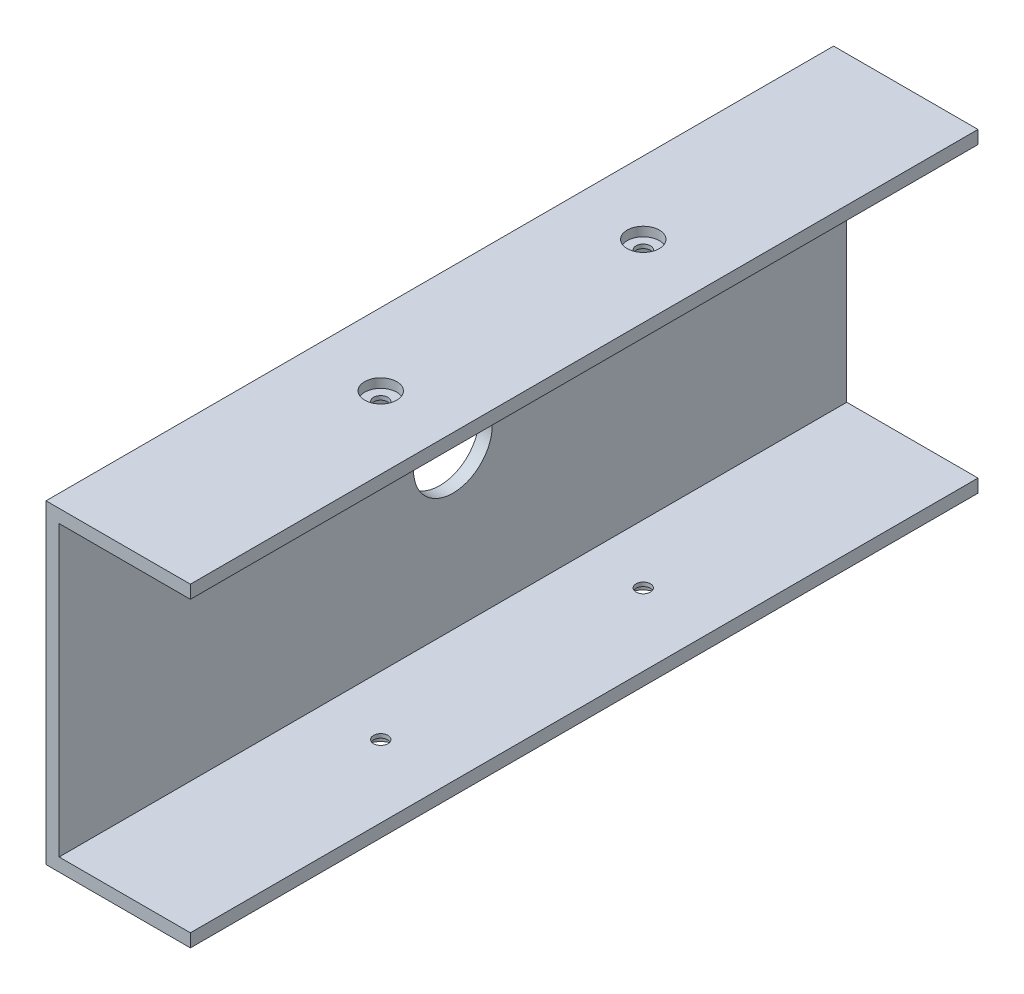
SolidWorks part; units mm, degrees
material "AISI 1035 Steel (SS)"
ref_plane "Front Plane" through (0, 0, 0) normal (0, 0, 1) x (1, 0, 0)
ref_plane "Top Plane" through (0, 0, 0) normal (0, 1, 0) x (1, 0, 0)
ref_plane "Right Plane" through (0, 0, 0) normal (1, 0, 0) x (0, 0, -1)
sketch "Sketch1" plane through (0, 0, 0) normal (0, 0, 1) x (1, 0, 0)
  line L0 (-64.6685, 67.8221) -> (-9.6685, 67.8221)
  line L1 (-9.6685, 67.8221) -> (-9.6685, 62.8221)
  line L2 (-9.6685, 62.8221) -> (-59.6685, 62.8221)
  line L3 (-59.6685, 62.8221) -> (-59.6685, -47.1779)
  line L4 (-59.6685, -47.1779) -> (-9.6685, -47.1779)
  line L5 (-9.6685, -47.1779) -> (-9.6685, -52.1779)
  line L6 (-9.6685, -52.1779) -> (-64.6685, -52.1779)
  line L7 (-64.6685, -52.1779) -> (-64.6685, 67.8221)
  point P6 (-64.6685, 7.8221)
  point P10 (-59.6685, 7.8221)
  dimension "D1" = 110
  dimension "D2" = 5
  dimension "D3" = 5
  dimension "D4" = 50
  dimension "D5" = 50
extrude "Boss-Extrude1" add sketch "Sketch1" along normal blind 300
sketch "Sketch2" plane through (0, 67.8221, 0) normal (0, 1, 0) x (1, 0, 0)
  line L0 (-64.6685, -300) -> (-64.6685, 0) construction
  line L1 (-9.6685, -300) -> (-9.6685, 0) construction
  line L2 (-9.6685, -300) -> (-64.6685, -300) construction
  point P0 (-37.1685, -200)
  point P1 (-32.1685, -200)
  dimension "D1" = 27.5
  dimension "D2" = 22.5
  dimension "D3" = 100
  dimension "D4" = 100
hole_wizard "CBORE for M5 Hex Head Bolt1" positions "Sketch3" profile "Sketch4" counterbore size "M5" standard "ISO"
sketch "Sketch3" plane through (0, 67.8221, 0) normal (0, 1, 0) x (1, 0, 0)
  point P0 (-37.1685, -200)
sketch "Sketch4" plane through (-37.1685, 67.8221, 200) normal (1, 0, 0) x (0, 0, 1)
  line L0 (0, 0) -> (0, 11.7024)
  line L1 (0, 11.7024) -> (2.75, 10.05)
  line L2 (2.75, 10.05) -> (2.75, 3.5)
  line L3 (2.75, 3.5) -> (6.119, 3.5)
  line L4 (6.119, 3.5) -> (6.119, 0)
  line L5 (6.119, 0) -> (0, 0)
  line L10 (0, 11.7024) -> (-2.75, 10.05) construction
  line L11 (0, -6.35) -> (0, 107.95) construction
  dimension "Hole Dia." = 5.5
  dimension "Hole Depth" = 10.05
  dimension "C'Bore Dia." = 12.238
  dimension "C'Bore Depth" = 3.5
  dimension "Drill Angle" = 118
pattern_linear "LPattern2" count 2 spacing 100 along (0, 0, -1) of "CBORE for M5 Hex Head Bolt1"
hole_wizard "CBORE for M5 Hex Head Bolt3" positions "Sketch7" profile "Sketch8" counterbore size "M5" standard "ISO"
sketch "Sketch7" plane through (0, -52.1779, 0) normal (0, -1, 0) x (-1, 0, 0)
  point P0 (37.1685, -200)
sketch "Sketch8" plane through (-37.1685, -52.1779, 200) normal (1, 0, 0) x (0, 0, -1)
  line L0 (0, 0) -> (0, 11.7024)
  line L1 (0, 11.7024) -> (2.75, 10.05)
  line L2 (2.75, 10.05) -> (2.75, 3.5)
  line L3 (2.75, 3.5) -> (6.119, 3.5)
  line L4 (6.119, 3.5) -> (6.119, 0)
  line L5 (6.119, 0) -> (0, 0)
  line L10 (0, 11.7024) -> (-2.75, 10.05) construction
  line L11 (0, -6.35) -> (0, 107.95) construction
  dimension "Hole Dia." = 5.5
  dimension "Hole Depth" = 10.05
  dimension "C'Bore Dia." = 12.238
  dimension "C'Bore Depth" = 3.5
  dimension "Drill Angle" = 118
pattern_linear "LPattern3" count 2 spacing 100 along (0, 0, -1) of "CBORE for M5 Hex Head Bolt3"
sketch "Sketch9" plane through (-64.6685, 0, 0) normal (-1, 0, 0) x (0, 0, 1)
  line L0 (300, 67.8221) -> (300, -52.1779) construction
  line L1 (300, 67.8221) -> (0, 67.8221) construction
  circle A0 centre (150, 12.8221) radius 15
  point P0 (150, 12.8221)
  dimension "D3" = 30
  dimension "D1" = 150
  dimension "D2" = 55
extrude "Cut-Extrude1" cut sketch "Sketch9" against normal through all
